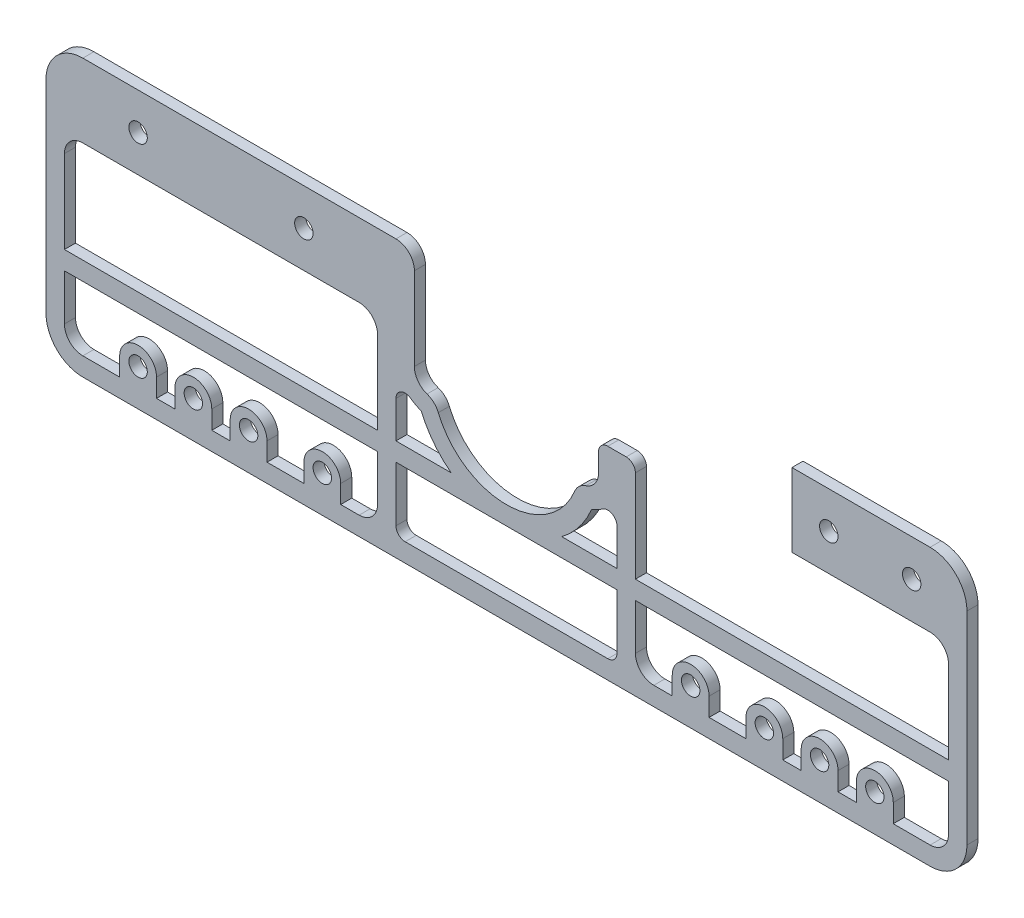
SolidWorks part; units mm, degrees
ref_plane "Front Plane" through (0, 0, 0) normal (0, 0, 1) x (1, 0, 0)
ref_plane "Top Plane" through (0, 0, 0) normal (0, 1, 0) x (1, 0, 0)
ref_plane "Right Plane" through (0, 0, 0) normal (1, 0, 0) x (0, 0, -1)
sketch "Sketch1" plane through (0, 0, 0) normal (0, 0, 1) x (1, 0, 0)
  line L0 (-40, 20) -> (-40, 55) construction
  line L4 (-250, -55) -> (-250, 3.1783)
  line L8 (-50, 75) -> (-230, 75) construction
  line L17 (0, -20) -> (0, -40)
  line L25 (0, -65) -> (0, -75)
  line L26 (0, 75) -> (0, -75) construction
  line L27 (-50, 95) -> (50, 95) construction
  line L34 (0, -75) -> (-230, -75)
  line L156 (-50, 75) -> (-230, 75) construction
  line L161 (0, -40) -> (0, -65)
  line L165 (-164.3309, 75) -> (-60, 75)
  line L167 (-230, 75) -> (-220, 75)
  line L171 (-250, 3.1783) -> (-250, 55)
  line L172 (-220, 75) -> (-164.3309, 75)
  line L173 (-50, 65) -> (-50, 20)
  arc A0 (-40, 20) -> (0, -20) centre (0, 20) ccw construction
  circle A1 centre (0, 20) radius 30 construction
  arc A4 (-230, -75) -> (-250, -55) centre (-230, -55) cw
  arc A5 (-250, 55) -> (-230, 75) centre (-230, 55) cw
  arc A124 (0, -20) -> (-37, 4.8013) centre (0, 20) cw
  arc A125 (-60, 75) -> (-50, 65) centre (-60, 65) cw
  arc A126 (-43.125, 10.5008) -> (-50, 20) centre (-40, 20) cw
  arc A127 (-37, 4.8013) -> (-43.125, 10.5008) centre (-46.25, 1.0016) ccw
  point P0 (0, 0)
  point P10 (-50, 10)
  point P11 (0, 50)
  point P30 (-40, 75)
  point P45 (0, -30)
  point P74 (0, 95)
  dimension "D3" = 80
  dimension "D4" = 60
  dimension "D6" = 55
  dimension "D7" = 75
  dimension "D10" = 10
  dimension "D11" = 20
  dimension "D8" = 10
  dimension "D5" = 10
  dimension "D9" = 20
  dimension "D13" = 210
  dimension "D16" = 100
  dimension "D17" = 20
  dimension "D26" = 250
extrude "Boss-Extrude1" add sketch "Sketch1" along normal blind 6
mirror "Mirror1" about plane through (0, -20, 6) normal (-1, 0, 0) of "Boss-Extrude1"
sketch "Sketch3" plane through (0, 0, 6) normal (0, 0, 1) x (1, 0, 0)
  line L0 (155, 75) -> (155, 35)
  line L1 (60, 75) -> (230, 75) construction
  line L2 (155, 35) -> (50, 35)
  line L3 (50, 20) -> (50, 65) construction
  line L4 (50, 20) -> (50, 65) construction
  line L5 (60, 75) -> (230, 75)
  line L6 (50, 65) -> (50, 35)
  line L7 (-60, 75) -> (-230, 75) construction
  line L8 (-250, 55) -> (-250, -55) construction
  line L9 (250, 55) -> (250, -55) construction
  arc A0 (60, 75) -> (50, 65) centre (60, 65) ccw construction
  arc A1 (60, 75) -> (50, 65) centre (60, 65) ccw
  circle A2 centre (175, 55) radius 5
  circle A3 centre (220, 55) radius 5
  circle A4 centre (-200, 55) radius 5
  circle A5 centre (-110, 55) radius 5
  line M15 (230, 75) -> (60, 75)
  arc M16 (60, 75) -> (50, 65) centre (60, 65) ccw
  line M17 (50, 65) -> (50, 20)
  dimension "D3" = 10
  dimension "D4" = 10
  dimension "D5" = 10
  dimension "D6" = 10
  dimension "D8" = 20
  dimension "D11" = 20
  dimension "D12" = 30
  dimension "D1" = 40
  dimension "D2" = 105
  dimension "D7" = 20
  dimension "D9" = 50
  dimension "D10" = 140
extrude "Cut-Extrude1" cut sketch "Sketch3" against normal through all contours L2 L0 M15 M16 M17 | A2 | A3 | A5 | A4 region at (102.7582, 54.9088, 6) region at (175, 55, 6) region at (220, 55, 6) region at (-110, 55, 6)
sketch "Sketch4" plane through (0, 0, 6) normal (0, 0, 1) x (1, 0, 0)
  line L0 (-230, -75) -> (230, -75) construction
  line L1 (-70, 25.101) -> (-70, -54.899)
  line L2 (-50, 20) -> (-50, 65) construction
  line L7 (-240, -55) -> (-240, 25.101)
  line L8 (-250, 55) -> (-250, -55) construction
  line L11 (-110, 35.101) -> (-80, 35.101)
  line L12 (-110, 35.101) -> (-140, 35.101)
  line L13 (-230, 35.101) -> (-140, 35.101)
  line L15 (-230, -65) -> (-210, -65)
  line L16 (-210, -65) -> (-210, -55)
  line L17 (-190, -55) -> (-190, -65)
  line L18 (-190, -65) -> (-110, -65)
  line L19 (-110, -65) -> (-110, -55)
  line L20 (-90, -55) -> (-90, -64.899)
  line L21 (-90, -64.899) -> (-80, -64.899)
  circle A1 centre (-200, -55) radius 5
  circle A2 centre (-100, -55) radius 5
  arc A6 (-230, -65) -> (-240, -55) centre (-230, -55) cw
  arc A12 (-210, -55) -> (-190, -55) centre (-200, -55) cw
  arc A13 (-110, -55) -> (-90, -55) centre (-100, -55) cw
  arc A14 (-240, 25.101) -> (-230, 35.101) centre (-230, 25.101) cw
  arc A15 (-70, -54.899) -> (-80, -64.899) centre (-80, -54.899) cw
  arc A16 (-70, 25.101) -> (-80, 35.101) centre (-80, 25.101) ccw
  point P0 (0, -75)
  dimension "D13" = 10
  dimension "D17" = 10
  dimension "D2" = 10
  dimension "D3" = 200
  dimension "D4" = 100
  dimension "D7" = 20
  dimension "D9" = 10
  dimension "D11" = 20
  dimension "D16" = 80
extrude "Cut-Extrude2" cut sketch "Sketch4" against normal through all contours L7 A6 L15 L16 | L13 | L17 L18 L19 | L20 L21 A15 L1 A16 L11 | A1 | A2 region at (-155.2296, -13.1384, 6) region at (-200, -55, 6) region at (-100, -55, 6)
mirror "Mirror2" about plane through (0, 0, 0) normal (1, 0, 0) of "Cut-Extrude2"
fillet "Fillet4" radius 5 1 edges at (50, 35, 3)
sketch "Sketch8" plane through (0, 0, 6) normal (0, 0, 1) x (1, 0, 0)
  line L0 (-60, 0) -> (-60, -64.899)
  line L2 (-60, -64.899) -> (60, -64.899)
  line L3 (60, -64.899) -> (60, 0)
  line L4 (-90, -64.899) -> (-80, -64.899) construction
  arc A0 (43.125, 10.5008) -> (50, 20) centre (40, 20) ccw construction
  arc A1 (43.125, 10.5008) -> (37, 4.8013) centre (46.25, 1.0016) ccw construction
  arc A2 (-37, 4.8013) -> (-43.125, 10.5008) centre (-46.25, 1.0016) ccw construction
  arc A3 (-50, 20) -> (-43.125, 10.5008) centre (-40, 20) ccw construction
  arc A4 (-37, 4.8013) -> (37, 4.8013) centre (0, 20) ccw construction
  arc A5 (43.125, 10.5008) -> (50, 20) centre (40, 20) ccw construction
  arc A6 (43.125, 10.5008) -> (37, 4.8013) centre (46.25, 1.0016) ccw construction
  arc A7 (-37, 4.8013) -> (-43.125, 10.5008) centre (-46.25, 1.0016) ccw construction
  arc A8 (-50, 20) -> (-43.125, 10.5008) centre (-40, 20) ccw construction
  arc A9 (-37, 4.8013) -> (37, 4.8013) centre (0, 20) ccw construction
  arc A10 (-52, 4) -> (-46.25, 1.0016) centre (-40, 20) ccw
  arc A11 (-46.25, 1.0016) -> (-46.25, 1.0016) centre (-46.25, 1.0016) ccw
  arc A12 (-46.25, 1.0016) -> (46.25, 1.0016) centre (0, 20) ccw
  arc A13 (46.25, 1.0016) -> (46.25, 1.0016) centre (46.25, 1.0016) ccw
  arc A14 (46.25, 1.0016) -> (52, 4) centre (40, 20) ccw
  arc A15 (46.25, 1.0016) -> (60, 20) centre (40, 20) ccw construction
  arc A16 (60, 0) -> (52, 4) centre (55, 0) ccw
  arc A17 (-60, 20) -> (-46.25, 1.0016) centre (-40, 20) ccw construction
  arc A18 (-60, 0) -> (-52, 4) centre (-55, 0) cw
  dimension "D2" = 5
  dimension "D1" = 10
extrude "Cut-Extrude5" cut sketch "Sketch8" against normal through all
fillet "Fillet5" radius 5 1 edges at (-60, -64.899, 3)
fillet "Fillet6" radius 5 1 edges at (60, -64.899, 3)
sketch "Sketch9" plane through (0, 0, 6) normal (0, 0, 1) x (1, 0, 0)
  line L0 (78.5825, 35) -> (55, 35) construction
  line L1 (78.5825, 35) -> (70, 35)
  line L2 (70, 25.101) -> (70, 35)
  arc A0 (78.5825, 35) -> (70, 25.101) centre (80, 25.101) ccw construction
  arc A1 (78.5825, 35) -> (70, 25.101) centre (80, 25.101) ccw
extrude "Cut-Extrude6" cut sketch "Sketch9" against normal through all
fillet "Fillet7" radius 5 1 edges at (70, 35, 3)
sketch "Sketch10" plane through (0, 0, 6) normal (0, 0, 1) x (1, 0, 0)
  line L0 (-250, -20) -> (250, -20)
  line L1 (-250, 55) -> (-250, -55) construction
  line L2 (250, 55) -> (250, -55) construction
  line L3 (250, -20) -> (250, -30)
  line L4 (250, -30) -> (-250, -30)
  line L5 (-250, -30) -> (-250, -20)
  arc A0 (-37, 4.8013) -> (37, 4.8013) centre (0, 20) ccw construction
  arc A1 (-46.25, 1.0016) -> (46.25, 1.0016) centre (0, 20) ccw construction
extrude "Boss-Extrude2" add sketch "Sketch10" against normal up to surface (6 mm away) up to face at (75.9484, -5.9001, 0)
sketch "Sketch11" plane through (0, 0, 6) normal (0, 0, 1) x (1, 0, 0)
  line L0 (-210, -65) -> (-210, -55) construction
  line L1 (-190, -55) -> (-190, -65) construction
  line L2 (-190, -55) -> (-190, -65)
  line L3 (-210, -65) -> (-210, -55)
  line L4 (-210, -65) -> (-190, -65)
  line L5 (-160, -55) -> (-160, -65)
  line L6 (-180, -65) -> (-180, -55)
  line L7 (-180, -65) -> (-160, -65)
  line L8 (-130, -55) -> (-130, -65)
  line L9 (-150, -65) -> (-150, -55)
  line L10 (-150, -65) -> (-130, -65)
  circle A0 centre (-200, -55) radius 5 construction
  arc A1 (-190, -55) -> (-210, -55) centre (-200, -55) ccw construction
  circle A2 centre (-200, -55) radius 5
  arc A3 (-190, -55) -> (-210, -55) centre (-200, -55) ccw
  circle A4 centre (-170, -55) radius 5
  arc A5 (-160, -55) -> (-180, -55) centre (-170, -55) ccw
  circle A6 centre (-140, -55) radius 5
  arc A7 (-130, -55) -> (-150, -55) centre (-140, -55) ccw
  dimension "D1" = 3
extrude "Boss-Extrude3" add sketch "Sketch11" against normal up to surface (6 mm away) contours L5 A5 L6 L7 A4 | L8 A7 L9 L10 A6 region at (-160.2828, -60, 6) region at (-130.2828, -60, 6) up to face at (152.1429, -54.5599, 0)
mirror "Mirror3" about plane through (0, 0, 0) normal (1, 0, 0) of "Boss-Extrude3"
